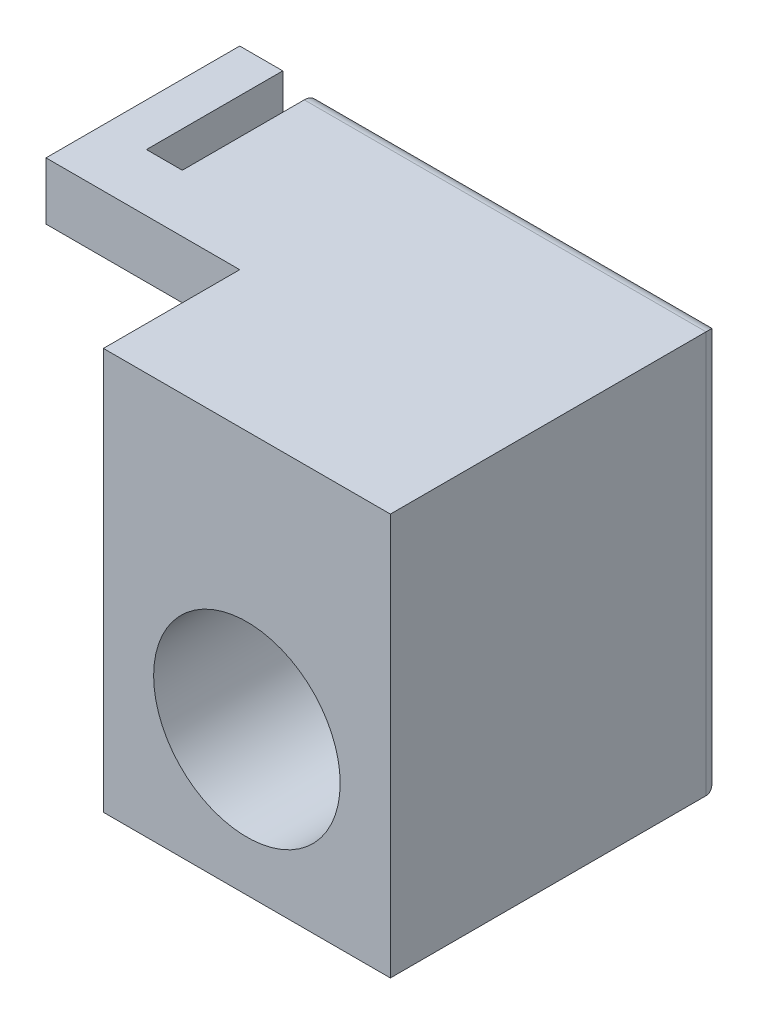
SolidWorks part; units mm, degrees
ref_plane "Front Plane" through (0, 0, 0) normal (0, 0, 1) x (1, 0, 0)
ref_plane "Top Plane" through (0, 0, 0) normal (0, 1, 0) x (1, 0, 0)
ref_plane "Right Plane" through (0, 0, 0) normal (1, 0, 0) x (0, 0, -1)
sketch "Sketch1" plane through (0, 0, 0) normal (0, 0, 1) x (1, 0, 0)
  line L1 (0, 0) -> (-20, 0)
  line L2 (0, 0) -> (0, -28)
  line L3 (0, -28) -> (-20, -28)
  line L4 (-20, 0) -> (-20, -28)
  dimension "D1" = 20
  dimension "D2" = 28
extrude "Boss-Extrude1" add sketch "Sketch1" along normal blind 23
sketch "Sketch2" plane through (0, 0, 23) normal (0, 0, 1) x (1, 0, 0)
  line L0 (-20, 0) -> (-20, -28) construction
  line L1 (0, 0) -> (-20, 0) construction
  circle A0 centre (-10, -18) radius 6.5
  point P4 (-20, -14)
  point P7 (-10, 0)
  dimension "D1" = 4
  dimension "D2" = 0
  dimension "D3" = 13
extrude "Cut-Extrude1" cut sketch "Sketch2" against normal blind 40
sketch "Sketch3" plane through (-20, 0, 0) normal (-1, 0, 0) x (0, 0, 1)
  line L1 (0, 0) -> (0, -28) construction
  circle A0 centre (8, -18) radius 2.75
  point P7 (0, -14)
  dimension "D1" = 8
  dimension "D2" = 4
  dimension "D3" = 5.5
extrude "Cut-Extrude2" cut sketch "Sketch3" against normal blind 10
thread "Thread1" pitch 2.1167 start angle 0, offset 0, length 10, pitch 2.1167, diameter 5.5
ref_plane "Plane1" through (-20, -18, 5.25) normal (0, -1, 0) x (0, 0, -1)
sketch "Thread Profile1" plane through (-20, -18, 5.25) normal (0, -1, 0) x (0, 0, -1)
  line L0 (0, 0) -> (0, 2.1167) construction
  line L1 (0, 0) -> (1.1457, 0.6615)
  line L2 (1.1457, 0.6615) -> (1.1457, 0.926)
  line L3 (1.1457, 0.926) -> (0, 1.5875)
  line L4 (1.1457, 0.7937) -> (0, 0.7937) construction
  line L11 (0, 0) -> (0, 1.5875)
  point P2 (0, 0)
  dimension "Pitch" = 2.1167
  dimension "Profile_Angle" = 60
  dimension "Profile_Land" = 0.2646
  dimension "Profile_Height" = 1.1457
sketch "Sketch6" plane through (-20, 0, 0) normal (-1, 0, 0) x (0, 0, 1)
  circle A0 centre (8, -18) radius 3.75
  dimension "D1" = 7.5
extrude "Cut-Extrude3" cut sketch "Sketch6" against normal blind 1
sketch "Sketch7" plane through (-20, 0, 0) normal (-1, 0, 0) x (0, 0, 1)
  line L0 (23, 0) -> (0, 0) construction
  line L1 (0, -4) -> (13.5, -4)
  line L2 (0, -4) -> (0, 0)
  line L3 (0, 0) -> (13.5, 0)
  line L4 (13.5, -4) -> (13.5, 0)
  line L5 (0, 0) -> (0, -28) construction
  dimension "D1" = 0
  dimension "D2" = 0
  dimension "D3" = 4
  dimension "D4" = 13.5
extrude "Boss-Extrude2" add sketch "Sketch7" along normal blind 13.5
sketch "Sketch8" plane through (0, -4, 0) normal (0, -1, 0) x (-1, 0, 0)
  line L0 (33.5, 0) -> (20, 0) construction
  line L1 (30.5, 0) -> (28, 0)
  line L2 (30.5, 0) -> (30.5, -9.5)
  line L3 (30.5, -9.5) -> (28, -9.5)
  line L4 (28, 0) -> (28, -9.5)
  line L5 (33.5, 0) -> (33.5, -13.5) construction
  dimension "D1" = 9.5
  dimension "D2" = 3
  dimension "D3" = 2.5
extrude "Cut-Extrude4" cut sketch "Sketch8" against normal blind 10
fillet "Fillet1" radius 1 5 edges at (-10, -28, 0) (-14, 0, 0) (0, -14, 0) (-20, -16, 0) (-24, -4, 0)
